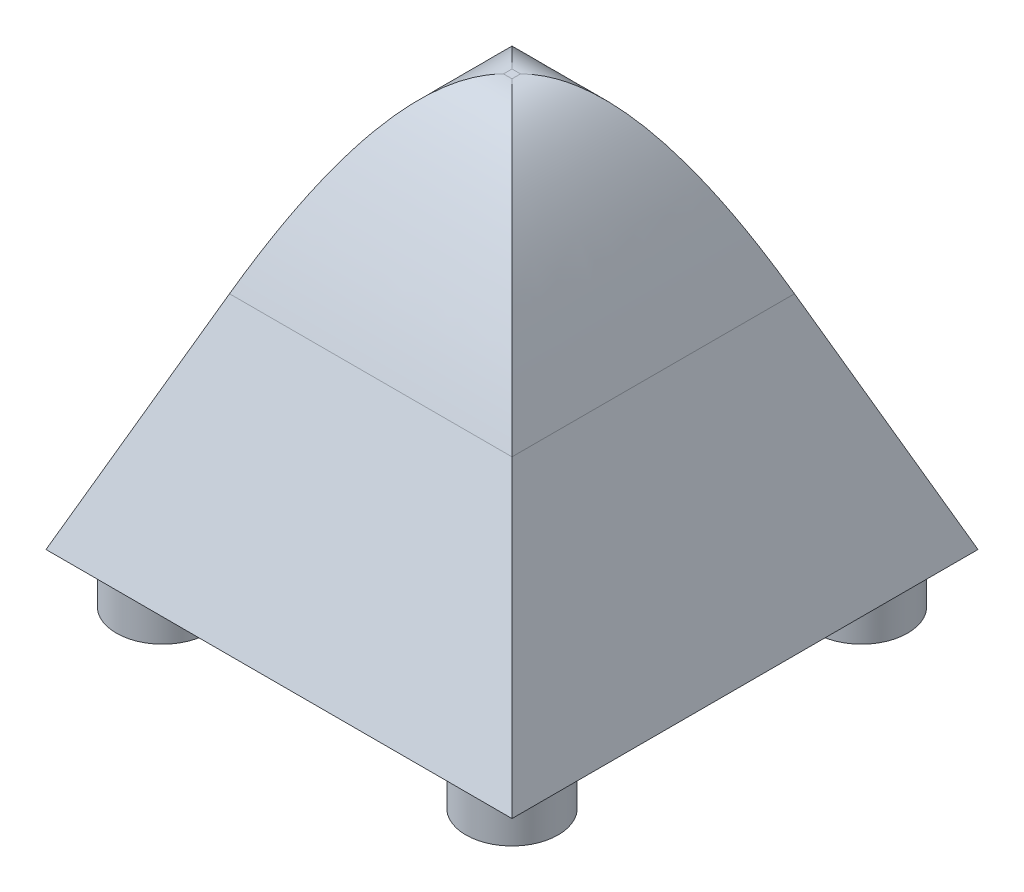
SolidWorks part; units mm, degrees
ref_plane "Plan de face" through (0, 0, 0) normal (0, 0, 1) x (1, 0, 0)
ref_plane "Plan de dessus" through (0, 0, 0) normal (0, 1, 0) x (1, 0, 0)
ref_plane "Plan de droite" through (0, 0, 0) normal (1, 0, 0) x (0, 0, -1)
sketch "Esquisse6" plane through (0, 0, 0) normal (0, 1, 0) x (1, 0, 0)
  line L1 (-14.1421, 14.1421) -> (14.1421, 14.1421)
  line L2 (-14.1421, 14.1421) -> (-14.1421, -14.1421)
  line L3 (-14.1421, -14.1421) -> (14.1421, -14.1421)
  line L4 (14.1421, 14.1421) -> (14.1421, -14.1421)
  line L5 (-14.1421, 14.1421) -> (14.1421, -14.1421) construction
  line L6 (-14.1421, -14.1421) -> (14.1421, 14.1421) construction
  point P0 (0, 0)
  dimension "D1" = 40
extrude "Boss.-Extru.2" add sketch "Esquisse6" along normal blind 25 draft 22.5
fillet "Congé3" radius 15 4 edges at (0, 25, 3.7868) (-3.7868, 25, 0) (0, 25, -3.7868) (3.7868, 25, 0)
sketch "Esquisse7" plane through (0, 0, 0) normal (0, -1, 0) x (1, 0, 0)
  line L0 (-14.1421, 14.1421) -> (14.1421, -14.1421) construction
  line L1 (-14.1421, -14.1421) -> (14.1421, 14.1421) construction
  circle A0 centre (-10.6066, 10.6066) radius 2.8
  circle A1 centre (10.6066, 10.6066) radius 2.8
  circle A2 centre (10.6066, -10.6066) radius 2.8
  circle A3 centre (-10.6066, -10.6066) radius 2.8
  point P5 (0, 0)
  point P10 (0, 0)
  point P18 (0, 0)
  point P19 (0, 0)
  point P20 (0, 0)
  point P21 (0, 0)
  point P22 (-6.8683, 6.8683)
  dimension "D1" = 5.6
  dimension "D2" = 30
extrude "Boss.-Extru.3" add sketch "Esquisse7" along normal blind 3
